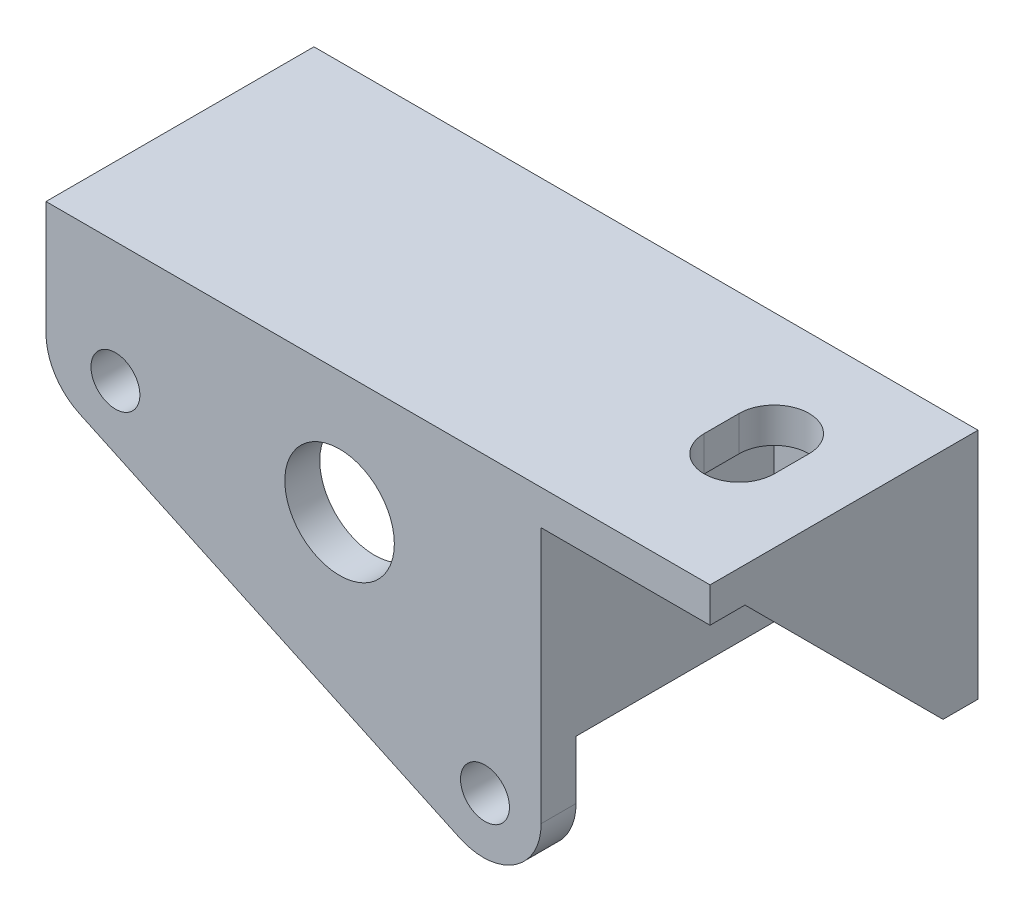
SolidWorks part; units mm, degrees
material "1060 Alloy"
ref_plane "Front Plane" through (0, 0, 0) normal (0, 0, 1) x (1, 0, 0)
ref_plane "Top Plane" through (0, 0, 0) normal (0, 1, 0) x (1, 0, 0)
ref_plane "Right Plane" through (0, 0, 0) normal (1, 0, 0) x (0, 0, -1)
sketch "Sketch1" plane through (0, 0, 0) normal (1, 0, 0) x (0, 0, -1)
  line L0 (0, 0) -> (-20, 0)
  line L1 (-20, 0) -> (-20, -3)
  line L2 (-20, -3) -> (-11.5, -11.5)
  line L3 (-11.5, -11.5) -> (0, 0) construction
  line L4 (-3, -20) -> (-11.5, -11.5)
  line L5 (0, -20) -> (-3, -20)
  line L6 (0, 0) -> (0, -20)
  dimension "D1" = 3
  dimension "D2" = 20
extrude "Boss-Extrude1" add sketch "Sketch1" along normal mid plane 17
sketch "Sketch2" plane through (0, 0, 0) normal (1, 0, 0) x (0, 0, -1)
  line L0 (-20, -3) -> (-3, -20) construction
  line L1 (-3, -3) -> (-20, -3)
  line L2 (-3, -3) -> (-3, -20)
  line L3 (-3, -20) -> (-20, -20)
  line L4 (-20, -3) -> (-20, -20)
  line L5 (-20, 0) -> (-20, -3) construction
extrude "Cut-Extrude1" cut sketch "Sketch2" against normal mid plane 12
sketch "Sketch3" plane through (0, 0, 3) normal (0, 0, 1) x (1, 0, 0)
  line L0 (0, -9) -> (0, -12) construction
  line L1 (-3, -9) -> (-3, -12)
  line L2 (3, -9) -> (3, -12)
  line L3 (0, -10.5) -> (0.7454, -10.5) construction
  line L4 (-6, -20) -> (6, -20) construction
  arc A0 (-3, -9) -> (3, -9) centre (0, -9) cw
  arc A1 (-3, -12) -> (3, -12) centre (0, -12) ccw
  dimension "D3" = 9
  dimension "D4" = 5
  dimension "D1" = 3
  dimension "D2" = 3
extrude "Cut-Extrude2" cut sketch "Sketch3" against normal up to next
sketch "Sketch4" plane through (0, 0, 0) normal (0, 0, -1) x (-1, 0, 0)
  line L0 (-1, -2.15) -> (1, -2.15) construction
  line L1 (-1, -3) -> (1, -3)
  line L2 (-1, -1.3) -> (1, -1.3)
  line L3 (0, 0) -> (0, -2.15) construction
  line L4 (-8.5, 0) -> (8.5, 0) construction
  line L5 (-2.1032, -9.8) -> (3, -9.8) construction
  line L6 (-1, -18.3) -> (1, -18.3)
  line L7 (-1, -16.6) -> (1, -16.6)
  line L8 (3, -12) -> (3, -9) construction
  arc A0 (-1, -3) -> (-1, -1.3) centre (-1, -2.15) cw
  arc A1 (1, -3) -> (1, -1.3) centre (1, -2.15) ccw
  arc A2 (1, -16.6) -> (1, -18.3) centre (1, -17.45) cw
  arc A3 (-1, -16.6) -> (-1, -18.3) centre (-1, -17.45) ccw
  dimension "D3" = 3.7
  dimension "D4" = 3
  dimension "D5" = 17
  dimension "D1" = 0.85
  dimension "D2" = 0.85
ref_plane "Plane1" through (0, 0, 0) normal (0, 0.7071, 0.7071) x (-1, 0, 0)
mirror "Mirror1" about plane through (0, 0, 0) normal (0, 0.7071, 0.7071) of "Cut-Extrude2"
sketch "Esboço1" plane through (-8.5, 0, 0) normal (-1, 0, 0) x (0, 0, 1)
  line L0 (0, 0) -> (0, -3)
  line L1 (0, -20) -> (0, 0) construction
  line L2 (0, -3) -> (20, -3)
  line L3 (20, -3) -> (20, 0)
  line L4 (20, 0) -> (0, 0)
extrude "Ressalto-extrusão1" add sketch "Esboço1" along normal blind 40
sketch "Esboço2" plane through (8.5, 0, 0) normal (1, 0, 0) x (0, 0, -1)
  line L0 (-20, 0) -> (-20, -30)
  line L1 (-20, -30) -> (-23, -30)
  line L2 (-23, -30) -> (-23, 0)
  line L3 (-23, 0) -> (-20, 0)
  dimension "D1" = 3
  dimension "D2" = 30
extrude "Ressalto-extrusão2" add sketch "Esboço2" against normal blind 57
sketch "Esboço3" plane through (0, 0, 20) normal (0, 0, -1) x (-1, 0, 0)
  line L0 (8.5, -3) -> (8.5, -20)
  line L2 (8.5, -20) -> (6, -20)
  line L3 (6, -20) -> (6, -3)
  line L4 (6, -3) -> (8.5, -3)
  dimension "D1" = 17
extrude "Ressalto-extrusão3" add sketch "Esboço3" along normal up to surface up to face at (7.25, -11.5, 11.5)
sketch "Esboço5" plane through (0, 0, 20) normal (0, 0, -1) x (-1, 0, 0)
  line L0 (6, -3) -> (6, -30)
  line L1 (48.5, -30) -> (-8.5, -30) construction
  line L2 (6, -30) -> (-8.5, -30)
  line L3 (-8.5, -30) -> (-8.5, -3)
  line L4 (-8.5, -3) -> (6, -3)
extrude "Corte-extrusão1" cut sketch "Esboço5" against normal through all
sketch "Esboço6" plane through (0, 0, 23) normal (0, 0, 1) x (1, 0, 0)
  line L0 (-48.5, -13) -> (-12.0434, -30)
  line L1 (-48.5, 0) -> (-48.5, -30) construction
  line L2 (-48.5, -30) -> (-6, -30) construction
  line L3 (-40.903, -14.9252) -> (-43.954, -13.5025) construction
  line L4 (-48.5, -13) -> (-48.5, -30)
  line L5 (-48.5, -30) -> (-12.0434, -30)
  dimension "D1" = 10
extrude "Corte-extrusão2" cut sketch "Esboço6" against normal through all
fillet "Filete1" radius 5 3 edges at (-48.5, -13, 21.5) (-12.0434, -30, 21.5) (-6, -30, 21.5)
sketch "Esboço7" plane through (0, 0, 23) normal (0, 0, 1) x (1, 0, 0)
  circle A0 centre (-42.5413, -10.3546) radius 2.1 construction
  circle A1 centre (-42.5413, -10.3546) radius 2.1
  circle A4 centre (-10.8206, -25.1463) radius 2.1 construction
  circle A5 centre (-10.8206, -25.1463) radius 2.1
  circle A6 centre (-23.3, -10.5) radius 4.7
extrude "Corte-extrusão3" cut sketch "Esboço7" against normal through all
